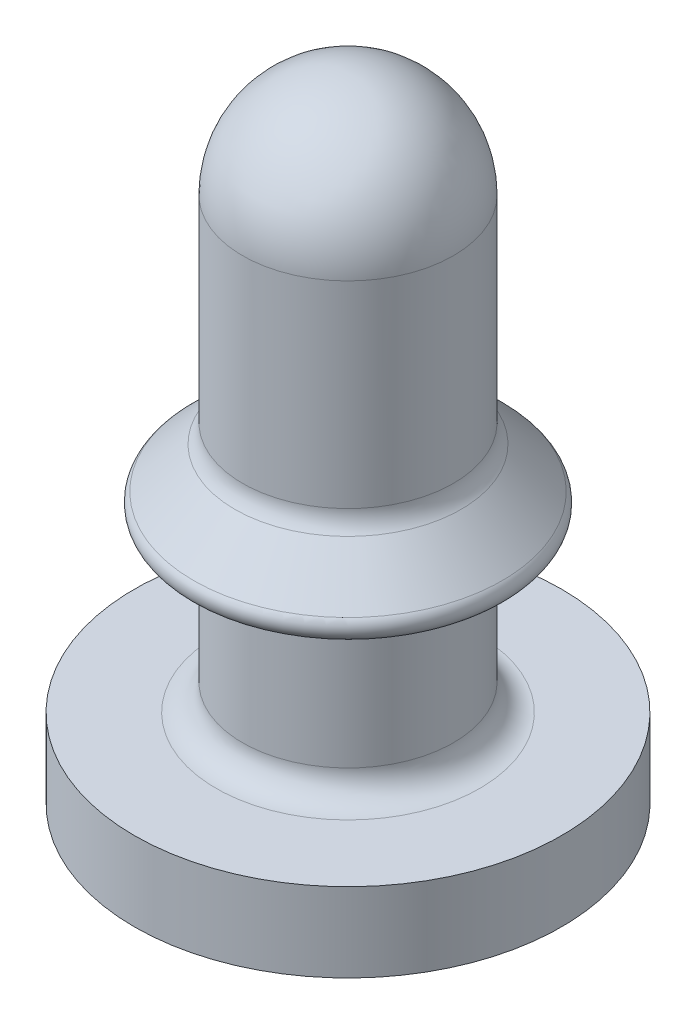
SolidWorks part; units mm, degrees
ref_plane "Front Plane" through (0, 0, 0) normal (0, 0, 1) x (1, 0, 0)
ref_plane "Top Plane" through (0, 0, 0) normal (0, 1, 0) x (1, 0, 0)
ref_plane "Right Plane" through (0, 0, 0) normal (1, 0, 0) x (0, 0, -1)
sketch "Sketch1" plane through (0, 0, 0) normal (0, 1, 0) x (1, 0, 0)
  circle A0 centre (0, 0) radius 2
  dimension "D1" = 4
extrude "Boss-Extrude1" add sketch "Sketch1" along normal blind 12
sketch "Sketch6" plane through (0, 0, 0) normal (0, -1, 0) x (1, 0, 0)
  circle A0 centre (0, 0) radius 4.05
  dimension "D1" = 8.1
extrude "Boss-Extrude3" add sketch "Sketch6" against normal blind 1.5
sketch "Sketch8" plane through (0, 0, 0) normal (0, 0, 1) x (1, 0, 0)
  line L0 (2, 6.0536) -> (2.9268, 5.1268)
  line L1 (2, 1.5) -> (2, 12) construction
  line L2 (2.75, 4.7) -> (2, 4.7)
  line L3 (2, 4.7) -> (2, 6.0536)
  line L5 (4.05, 1.5) -> (-4.05, 1.5) construction
  line L6 (0, 0) -> (0, 12) construction
  line L7 (-4.05, 0) -> (4.05, 0) construction
  line L8 (2, 12) -> (-2, 12) construction
  arc A0 (2.75, 4.7) -> (2.9268, 5.1268) centre (2.75, 4.95) ccw
  dimension "D3" = 0.5
  dimension "D4" = 6
  dimension "D1" = 3.2
  dimension "D2" = 45
revolve "Revolve1" add sketch "Sketch8" angle 360 about L6
sketch "Sketch2" plane through (0, 0, 0) normal (0, -1, 0) x (1, 0, 0)
  circle A0 centre (0, 0) radius 1
  dimension "D1" = 2
extrude "Cut-Extrude1" cut sketch "Sketch2" against normal blind 10
draft "Draft1" type of draft neutral plane draft angle 1 faces to draft 1 face at (0, 10, -1) neutral plane through (0, 10, 0) neutral plane normal (0, -1, 0) parameters "D1"=1
sketch "Sketch7" plane through (0, 0, 0) normal (0, 0, 1) x (1, 0, 0)
  line L0 (2, 6.0536) -> (2, 12) construction
  line L1 (2, 12) -> (-2, 12) construction
  line L4 (0, 10) -> (0, 12) construction
  line L5 (2, 10) -> (3.0807, 10)
  line L6 (3.0807, 10) -> (3.0807, 13.0807)
  line L7 (3.0807, 13.0807) -> (0, 13.0807)
  line L8 (0, 13.0807) -> (0, 12)
  arc A0 (2, 10) -> (0, 12) centre (0, 10) ccw
  point P5 (3.8101, 10.5)
  point P11 (4.5807, 14.2583)
  dimension "D1" = 3.0807
revolve "Cut-Revolve3" cut sketch "Sketch7" angle 360 about L4
sketch "Sketch3" plane through (0, 10, 0) normal (0, -1, 0) x (1, 0, 0)
  line L0 (1.151, 0.2338) -> (0.746, 0)
  line L1 (0.746, 0) -> (1.151, -0.2338)
  line L2 (0, 0) -> (1.1746, 0) construction
  line L3 (1.151, 0.2338) -> (1.151, -0.2338) construction
  line L6 (-0.373, -1.1138) -> (-0.373, -0.6461)
  line L7 (-0.373, -0.6461) -> (-0.778, -0.8799)
  line L10 (-0.373, -1.1138) -> (-0.778, -0.8799) construction
  line L11 (-0.778, 0.8799) -> (-0.373, 0.6461)
  line L14 (-0.373, 0.6461) -> (-0.373, 1.1138)
  line L15 (-0.778, 0.8799) -> (-0.373, 1.1138) construction
  arc A1 (-0.778, -0.8799) -> (-0.373, -1.1138) centre (0, 0) ccw
  arc A2 (-0.373, 1.1138) -> (-0.778, 0.8799) centre (0, 0) ccw
  circle A7 centre (0, 0) radius 1.1746 construction
  arc A8 (1.151, -0.2338) -> (1.151, 0.2338) centre (0, 0) ccw
  circle A9 centre (0, 0) radius 1 construction
  point P16 (0, 0)
  dimension "D1" = 0.254
extrude "Boss-Extrude2" add sketch "Sketch3" along normal up to surface (10 mm away) up to face at (0, 0, 1.1746)
sketch "ref_for_revolve" plane through (0, 0, 0) normal (0, -1, 0) x (1, 0, 0)
  circle A0 centre (0, 0) radius 1.1746 construction
sketch "Sketch4" plane through (0, 0, 0) normal (0, 0, 1) x (1, 0, 0)
  line L1 (1.1746, 0) -> (0.746, 0.4286)
  line L2 (0.746, 0.4286) -> (0, 0.4286)
  line L4 (0, 0.4286) -> (0, 0)
  line L5 (0.746, 0.4286) -> (0.746, 0) construction
  line L6 (0.746, 0) -> (1.1746, 0) construction
  line L7 (1.1746, 0) -> (0, 0)
  line L8 (-0.373, 0) -> (1.151, 0) construction
  line L9 (-1.1746, 0) -> (1.1746, 0) construction
  point P7 (0, 0)
  point P8 (1.2819, 0)
  point P12 (0, 0)
  point P13 (1.368, 0)
  point P14 (1.1559, 0)
  point P17 (0, 0)
revolve "Cut-Revolve1" cut sketch "Sketch4" angle 360 about L4
fillet "Fillet1" radius 0.5 3 edges at (0, 1.5, -2) (0, 4.7, -2) (0, 6.0536, -2)
